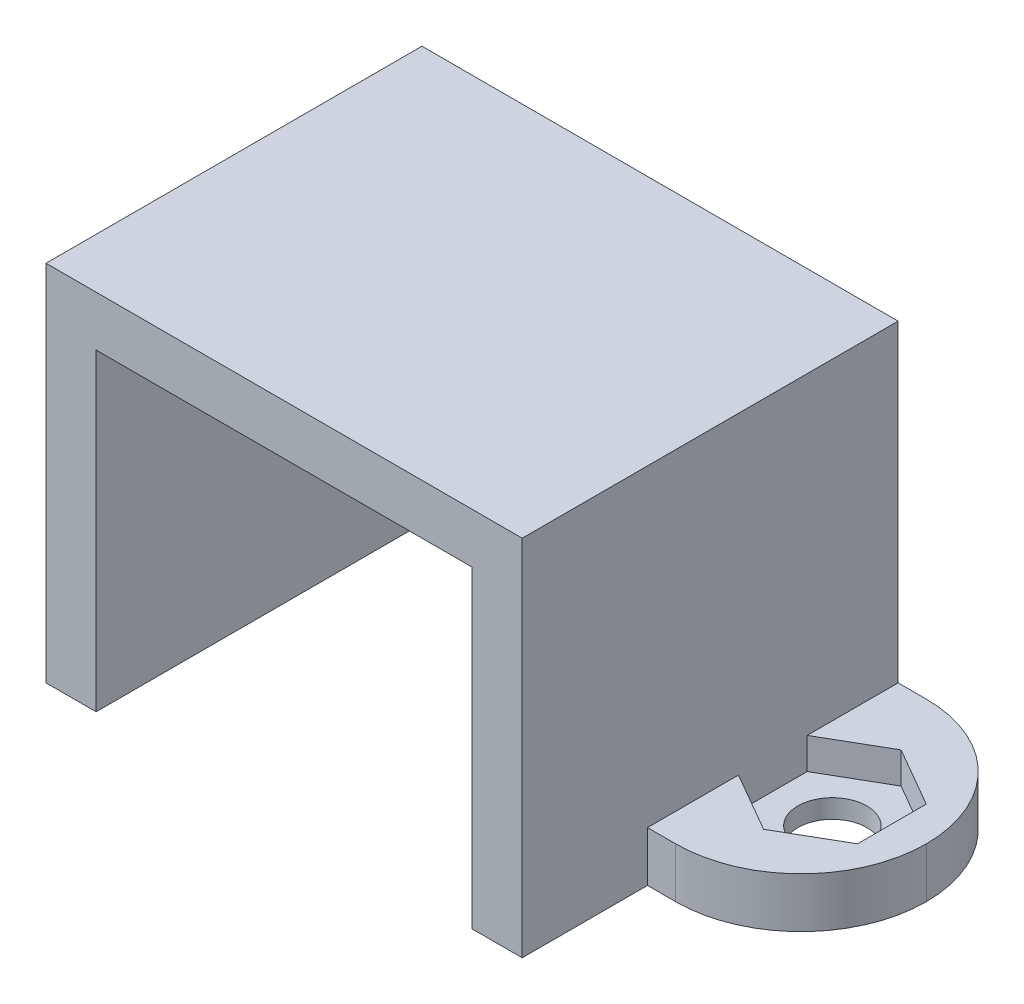
SolidWorks part; units mm, degrees
ref_plane "Front" through (0, 0, 0) normal (0, 0, 1) x (1, 0, 0)
ref_plane "Top" through (0, 0, 0) normal (0, 1, 0) x (1, 0, 0)
ref_plane "Right" through (0, 0, 0) normal (1, 0, 0) x (0, 0, -1)
sketch "草圖1" plane through (0, 0, 0) normal (0, 0, 1) x (1, 0, 0)
  line L0 (-12.5, -10) -> (-6, -10)
  line L1 (-6, -10) -> (-6, 0)
  line L2 (-6, 0) -> (6, 0)
  line L3 (6, 0) -> (6, -10)
  line L4 (6, -10) -> (12.5, -10)
  dimension "D1" = 12
  dimension "D2" = 10
  dimension "D3" = 6.5
  dimension "D4" = 6.5
  dimension "D5" = 10
extrude "伸長-薄件1" add sketch "草圖1" along normal blind 12 thin thin type one direction reverse wall 1.6
sketch "草圖2" plane through (0, -8.4, 0) normal (0, 1, 0) x (1, 0, 0)
  line L0 (-9.5, -4) -> (9.5, -4) construction
  line L2 (-7.6, 0) -> (7.6, 0) construction
  line L4 (0, 0) -> (0, -4) construction
  circle A0 centre (9.5, -4) radius 1.1
  circle A1 centre (-9.5, -4) radius 1.1
  dimension "D2" = 2.2
  dimension "D3" = 4
  dimension "D4" = 19
extrude "除料-伸長1" cut sketch "草圖2" against normal blind 10
sketch "草圖3" plane through (0, -10, 0) normal (0, -1, 0) x (1, 0, 0)
  line L1 (-12.5, 12) -> (-7.6, 12)
  line L2 (-12.5, 12) -> (-12.5, 8)
  line L3 (-12.5, 8) -> (-7.6, 8)
  line L4 (-7.6, 12) -> (-7.6, 8)
  line L6 (12.5, 12) -> (7.6, 12)
  line L7 (12.5, 12) -> (12.5, 8)
  line L8 (12.5, 8) -> (7.6, 8)
  line L9 (7.6, 12) -> (7.6, 8)
  line L10 (-7.6, 12) -> (-7.6, 0) construction
  line L11 (7.6, 12) -> (7.6, 0) construction
  point P4 (-7.6, 8)
  point P11 (7.6, 8)
  point P14 (-7.6, 12)
  point P15 (7.6, 12)
  point P18 (-12.5, 12)
  point P21 (12.5, 12)
  dimension "D1" = 4
  dimension "D2" = 4
extrude "除料-伸長2" cut sketch "草圖3" against normal blind 1.6
fillet "圓角1" radius 4 4 edges at (-12.5, -9.2, 0) (-12.5, -9.2, 8) (12.5, -9.2, 0) (12.5, -9.2, 8)
sketch "草圖4" plane through (0, -8.4, 0) normal (0, 1, 0) x (1, 0, 0)
  line L0 (-7.6, -12) -> (-7.6, 0) construction
  line L1 (-7.6, -5.097) -> (-7.6, -2.903)
  line L2 (-7.6, -2.903) -> (-9.5, -1.8061)
  line L3 (-9.5, -1.8061) -> (-11.4, -2.903)
  line L4 (-11.4, -2.903) -> (-11.4, -5.097)
  line L5 (-11.4, -5.097) -> (-9.5, -6.1939)
  line L6 (-9.5, -6.1939) -> (-7.6, -5.097)
  line L7 (7.6, -5.097) -> (9.5, -6.1939)
  line L8 (9.5, -6.1939) -> (11.4, -5.097)
  line L9 (11.4, -5.097) -> (11.4, -2.903)
  line L10 (11.4, -2.903) -> (9.5, -1.8061)
  line L11 (9.5, -1.8061) -> (7.6, -2.903)
  line L12 (7.6, -2.903) -> (7.6, -5.097)
  line L13 (7.6, -8) -> (7.6, 0) construction
  circle A0 centre (-9.5, -4) radius 1.9 construction
  circle A1 centre (9.5, -4) radius 1.9 construction
  point P10 (-7.4811, -5.1656)
  point P21 (0, 0)
extrude "除料-伸長3" cut sketch "草圖4" against normal blind 1
equation "\"1。5\"=10"
